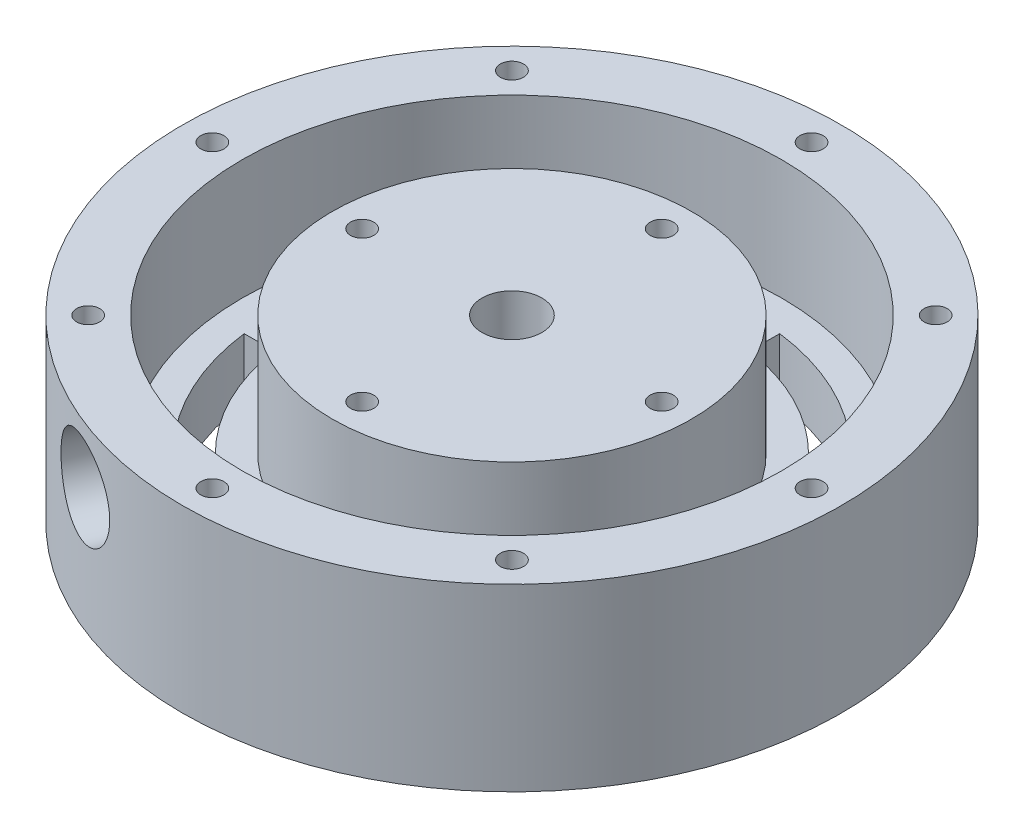
SolidWorks part; units mm, degrees
material "AISI 316 Annealed Stainless Steel Bar (SS)"
ref_plane "Front Plane" through (0, 0, 0) normal (0, 0, 1) x (1, 0, 0)
ref_plane "Top Plane" through (0, 0, 0) normal (0, 1, 0) x (1, 0, 0)
ref_plane "Right Plane" through (0, 0, 0) normal (1, 0, 0) x (0, 0, -1)
sketch "Sketch2" plane through (0, 0, 0) normal (0, 1, 0) x (1, 0, 0)
  line L0 (-6.35, 43.9941) -> (-6.35, 50.4016)
  line L1 (-50.4016, 6.35) -> (-43.9941, 6.35)
  line L2 (-43.9941, -6.35) -> (-50.4016, -6.35)
  line L3 (-6.35, -50.4016) -> (-6.35, -43.9941)
  line L4 (6.35, -43.9941) -> (6.35, -50.4016)
  line L5 (50.4016, -6.35) -> (43.9941, -6.35)
  line L6 (43.9941, 6.35) -> (50.4016, 6.35)
  line L7 (6.35, 50.4016) -> (6.35, 43.9941)
  arc A0 (-6.35, 43.9941) -> (-43.9941, 6.35) centre (0, 0) ccw
  arc A1 (-43.9941, -6.35) -> (-6.35, -43.9941) centre (0, 0) ccw
  arc A2 (6.35, -43.9941) -> (43.9941, -6.35) centre (0, 0) ccw
  arc A3 (6.35, 43.9941) -> (43.9941, 6.35) centre (0, 0) cw
  arc A4 (-6.35, 50.4016) -> (-50.4016, 6.35) centre (0, 0) ccw
  arc A5 (-50.4016, -6.35) -> (-6.35, -50.4016) centre (0, 0) ccw
  arc A6 (6.35, -50.4016) -> (50.4016, -6.35) centre (0, 0) ccw
  arc A7 (50.4016, 6.35) -> (6.35, 50.4016) centre (0, 0) ccw
  circle A8 centre (0, 0) radius 6.35
  circle A9 centre (0, 0) radius 57.15
  circle A10 centre (0, 0) radius 69.85
  circle A11 centre (0, 0) radius 38.1
  dimension "D1" = 50.8
  dimension "D2" = 6.35
  dimension "D4" = 12.7
  dimension "D5" = 6.35
  dimension "D6" = 12.7
  dimension "D7" = 6.35
  dimension "D3" = 12.7
extrude "Boss-Extrude2" add sketch "Sketch2" along normal blind 25.4 separate body contours A11 A8 | A10 A9 region at (-67.8743, 0, 0) region at (-37.0224, 0, 0)
extrude "Boss-Extrude3" add sketch "Sketch2<5>" against normal blind 12.7 contours A9 A11 A4 L0 A0 L1 A5 L2 A1 L3 A6 L4 A2 L5 A7 L6 A3 L7 | A10 A9 | A11 A8 region at (-55.5336, 0, 0) region at (-67.8743, 0, 0) region at (-37.0224, 0, 0)
sketch "Sketch2<5>" plane through (0, 0, 0) normal (0, 1, 0) x (1, 0, 0) same geometry as "Sketch2"
hole_wizard "#10 (0.1935) Diameter Hole1" positions "Sketch3" profile "Sketch4" hole size "#10" standard "ANSI Inch" end condition through all
sketch "Sketch3" plane through (0, 25.4, 0) normal (0, 1, 0) x (1, 0, 0)
  line L0 (0, -57.15) -> (0, -69.85) construction
  circle A0 centre (0, 0) radius 57.15 construction
  circle A1 centre (0, 0) radius 69.85 construction
  point P0 (0, -63.5)
  point P13 (0, 0)
  point P14 (6.2018, -61.1151)
sketch "Sketch4" plane through (0, 25.4, 63.5) normal (1, 0, 0) x (0, 0, 1)
  line L0 (0, 0) -> (0, 38.1)
  line L1 (0, 38.1) -> (2.4574, 38.1)
  line L2 (2.4574, 38.1) -> (2.4574, 0)
  line L5 (2.4574, 0) -> (0, 0)
  line L11 (0, -6.35) -> (0, 107.95) construction
  dimension "Thru Hole Dia." = 4.9149
  dimension "Thru Hole Depth" = 38.1
pattern_circular "CirPattern1" count 8 over 360 about axis through (0, -12.7, 0) along (0, 1, 0) of "#10 (0.1935) Diameter Hole1" reverse direction yes
hole_wizard "#10 (0.1935) Diameter Hole2" positions "3DSketch1" profile "Sketch5" hole size "#10" standard "ANSI Inch" end condition through all
sketch3d "3DSketch1"
  line L2 (0, -12.7, 6.35) -> (0, -12.7, 31.75) construction
  line L4 (0, -12.7, 6.35) -> (16.355, -12.7, 6.35) construction
  circle A0 centre (0, -12.7, 0) radius 6.35 construction
  point P0 (0, -12.7, 31.75)
  point P11 (0, -6.35, 0)
  point P18 (0, 0, 0)
  dimension "D1" = 25.4
sketch "Sketch5" plane through (0, -12.7, 31.75) normal (1, 0, 0) x (0, 0, -1)
  line L0 (0, 0) -> (0, 38.1)
  line L1 (0, 38.1) -> (2.4574, 38.1)
  line L2 (2.4574, 38.1) -> (2.4574, 0)
  line L5 (2.4574, 0) -> (0, 0)
  line L11 (0, -6.35) -> (0, 107.95) construction
  dimension "Thru Hole Dia." = 4.9149
  dimension "Thru Hole Depth" = 38.1
pattern_circular "CirPattern2" count 4 over 360 about axis through (0, -12.7, 0) along (0, 1, 0) of "#10 (0.1935) Diameter Hole2"
ref_plane "Plane1" through (-26.7304, 0, 64.533) normal (-0.3827, 0, 0.9239) x (0, 1, 0)
sketch "Sketch6" plane through (-26.7304, 0, 64.533) normal (-0.3827, 0, 0.9239) x (0, 1, 0)
  line L0 (12.7, 0) -> (25.4, 0) construction
  line L2 (25.4, -69.85) -> (25.4, 69.85) construction
  circle A0 centre (12.7, 0) radius 9.525
  point P2 (0, 0)
  point P7 (0, 0)
  dimension "D1" = 19.05
  dimension "D2" = 12.7
extrude "Cut-Extrude1" cut sketch "Sketch6" against normal up to next
